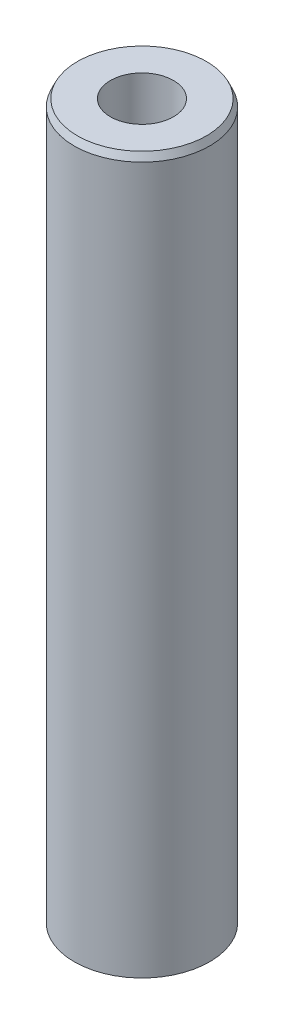
SolidWorks part; units mm, degrees
ref_plane "Front Plane" through (0, 0, 0) normal (0, 0, 1) x (1, 0, 0)
ref_plane "Top Plane" through (0, 0, 0) normal (0, 1, 0) x (1, 0, 0)
ref_plane "Right Plane" through (0, 0, 0) normal (1, 0, 0) x (0, 0, -1)
sketch "Sketch1" plane through (0, 0, 0) normal (0, 1, 0) x (1, 0, 0)
  circle A0 centre (0, 0) radius 50
  dimension "SHAFT_OD" = 100
extrude "Boss-Extrude1" add sketch "Sketch1" along normal blind 529.2872
sketch "Sketch2" plane through (0, 0, 0) normal (0, 1, 0) x (1, 0, 0)
  circle A0 centre (0, 0) radius 23.2698
  dimension "BORE_D" = 46.5396
extrude "Cut-Extrude1" cut sketch "Sketch2" along normal through all
chamfer "Chamfer1" distance 5.2831 angle 24.444 2 edges at (0, 529.2872, 50) (0, 0, 50) first distance on face at (0, 529.2872, 50) first distance on face at (0, 0, 23.2698)
